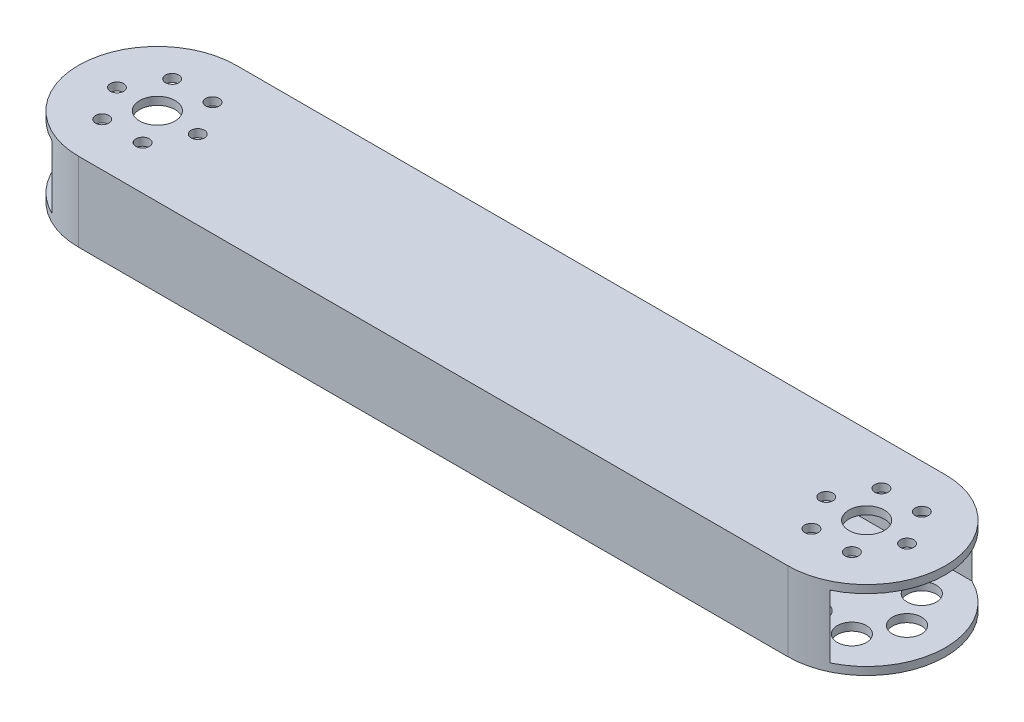
SolidWorks part; units mm, degrees
note: The reader was unsure of these and kept them because the rebuilt part matched: shared geometry of "Skizze2<3>".
ref_plane "Ebene vorne" through (0, 0, 0) normal (0, 0, 1) x (1, 0, 0)
ref_plane "Ebene oben" through (0, 0, 0) normal (0, 1, 0) x (1, 0, 0)
ref_plane "Ebene rechts" through (0, 0, 0) normal (1, 0, 0) x (0, 0, -1)
sketch "Skizze1" plane through (0, 0, 0) normal (1, 0, 0) x (0, 0, -1)
  line L0 (-18, 8) -> (18, 8)
  line L1 (-20, 10) -> (20, 10)
  line L2 (-20, 10) -> (-20, -10)
  line L3 (-20, -10) -> (20, -10)
  line L4 (20, 10) -> (20, -10)
  line L5 (-20, 10) -> (20, -10) construction
  line L6 (-20, -10) -> (20, 10) construction
  line L7 (18, 8) -> (18, -8)
  line L8 (-18, -8) -> (18, -8)
  line L9 (-18, 8) -> (-18, -8)
  point P0 (0, 0)
  dimension "D1" = 40
  dimension "D2" = 20
  dimension "D3" = 2
extrude "Aufsatz-Linear austragen1" add sketch "Skizze1" along normal blind 220 contours L0 L9 L8 L7 | L1 L4 L3 L2
sketch "Skizze2" plane through (0, 10, 0) normal (0, 1, 0) x (1, 0, 0)
  line L0 (0, 0) -> (20, 0) construction
  line L1 (220, 0) -> (200, 0) construction
  line L2 (20, 0) -> (30.25, 0) construction
  line L3 (200, 0) -> (189.75, 0) construction
  line L4 (0, 20) -> (0, -20)
  line L5 (0, -20) -> (220, -20)
  line L6 (220, -20) -> (220, 20)
  line L7 (220, 20) -> (0, 20)
  line L8 (0, 20) -> (0, -20) construction
  line L10 (220, -20) -> (220, 20) construction
  line L11 (20, 20) -> (0, 20)
  line L12 (0, 20) -> (0, -20)
  line L13 (0, -20) -> (20, -20)
  line L14 (200, 20) -> (220, 20)
  line L15 (220, 20) -> (220, 0)
  line L16 (220, 0) -> (220, -20)
  line L17 (220, -20) -> (200, -20)
  circle A2 centre (30.25, 0) radius 1.7
  circle A3 centre (189.75, 0) radius 1.7
  circle A4 centre (25.125, -8.8768) radius 1.7
  circle A5 centre (14.875, -8.8768) radius 1.7
  circle A6 centre (9.75, 0) radius 1.7
  circle A7 centre (14.875, 8.8768) radius 1.7
  circle A8 centre (25.125, 8.8768) radius 1.7
  circle A9 centre (194.875, 8.8768) radius 1.7
  circle A10 centre (205.125, 8.8768) radius 1.7
  circle A11 centre (210.25, 0) radius 1.7
  circle A12 centre (205.125, -8.8768) radius 1.7
  circle A13 centre (194.875, -8.8768) radius 1.7
  arc A14 (20, 20) -> (20, -20) centre (20, 0) ccw
  arc A15 (200, -20) -> (200, 20) centre (200, 0) ccw
  circle A16 centre (20, 0) radius 4.5
  circle A17 centre (200, 0) radius 4.5
  dimension "D5" = 3.4
  dimension "D6" = 6
  dimension "D2" = 20
  dimension "D4" = 10.25
  dimension "D1" = 0
  dimension "D7" = 6
extrude "Schnitt-Linear austragen1" cut sketch "Skizze2" against normal through all
sketch "Skizze4" plane through (0, -10, 0) normal (0, -1, 0) x (1, 0, 0)
  circle A0 centre (189.75, 0) radius 1.7 construction
  circle A1 centre (194.875, -8.8768) radius 1.7 construction
  circle A2 centre (205.125, -8.8768) radius 1.7 construction
  circle A3 centre (210.25, 0) radius 1.7 construction
  circle A4 centre (205.125, 8.8768) radius 1.7 construction
  circle A5 centre (194.875, 8.8768) radius 1.7 construction
  circle A6 centre (30.25, 0) radius 1.7 construction
  circle A7 centre (25.125, -8.8768) radius 1.7 construction
  circle A8 centre (14.875, -8.8768) radius 1.7 construction
  circle A9 centre (9.75, 0) radius 1.7 construction
  circle A10 centre (25.125, 8.8768) radius 1.7 construction
  circle A11 centre (14.875, 8.8768) radius 1.7 construction
  circle A12 centre (189.75, 0) radius 1.7 construction
  circle A13 centre (194.875, -8.8768) radius 1.7 construction
  circle A14 centre (205.125, -8.8768) radius 1.7 construction
  circle A15 centre (210.25, 0) radius 1.7 construction
  circle A16 centre (205.125, 8.8768) radius 1.7 construction
  circle A17 centre (194.875, 8.8768) radius 1.7 construction
  circle A18 centre (30.25, 0) radius 1.7 construction
  circle A19 centre (25.125, -8.8768) radius 1.7 construction
  circle A20 centre (14.875, -8.8768) radius 1.7 construction
  circle A21 centre (9.75, 0) radius 1.7 construction
  circle A22 centre (25.125, 8.8768) radius 1.7 construction
  circle A23 centre (14.875, 8.8768) radius 1.7 construction
  circle A24 centre (189.75, 0) radius 3.7
  circle A25 centre (194.875, -8.8768) radius 3.7
  circle A26 centre (205.125, -8.8768) radius 3.7
  circle A27 centre (210.25, 0) radius 3.7
  circle A28 centre (205.125, 8.8768) radius 3.7
  circle A29 centre (194.875, 8.8768) radius 3.7
  circle A30 centre (30.25, 0) radius 3.7
  circle A31 centre (25.125, -8.8768) radius 3.7
  circle A32 centre (14.875, -8.8768) radius 3.7
  circle A33 centre (9.75, 0) radius 3.7
  circle A34 centre (25.125, 8.8768) radius 3.7
  circle A35 centre (14.875, 8.8768) radius 3.7
  dimension "D1" = 2
extrude "Schnitt-Linear austragen2" cut sketch "Skizze4" against normal blind 5
extrude "Schnitt-Linear austragen3" cut sketch "Skizze2<3>" against normal blind 5 contours A16 | A17
sketch "Skizze2<3>" plane through (0, 10, 0) normal (0, 1, 0) x (1, 0, 0) same geometry as "Skizze2"
